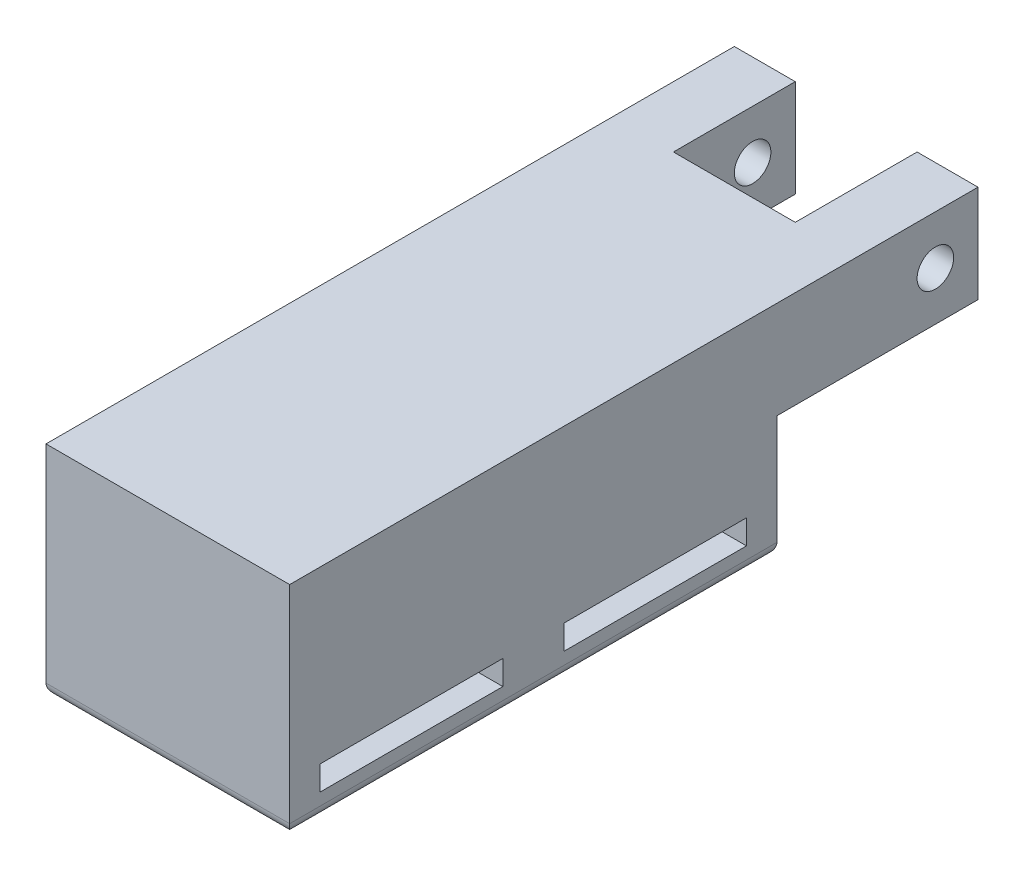
SolidWorks part; units mm, degrees
ref_plane "Alzado" through (0, 0, 0) normal (0, 0, 1) x (1, 0, 0)
ref_plane "Planta" through (0, 0, 0) normal (0, 1, 0) x (1, 0, 0)
ref_plane "Vista lateral" through (0, 0, 0) normal (1, 0, 0) x (0, 0, -1)
sketch "Croquis1" plane through (0, 0, 0) normal (1, 0, 0) x (0, 0, -1)
  line L0 (0, 9) -> (0, 1) construction
  line L9 (-1.5, 9) -> (-58, 9)
  line L18 (0, 9) -> (0, -9) construction
  line L19 (0, -9) -> (-58, -9) construction
  line L25 (0, 1) -> (-18, 1) construction
  line L26 (0, 1) -> (0, -2.6179) construction
  line L29 (0, -2.6179) -> (0, -9) construction
  line L31 (-1.5, 9) -> (-1.5, 1)
  line L32 (-18, 1) -> (-1.5, 1)
  line L35 (-58, -9) -> (-18, -9)
  line L56 (-58, 9) -> (-58, -9)
  line L59 (0, 9) -> (-58, 9) construction
  line L61 (-18, 1) -> (-18, -9)
  circle A0 centre (-5, 5) radius 1.5
  point P5 (0, 0)
  point P7 (0, 0)
  point P9 (0, 0)
  point P11 (-32.3135, 7.75)
  point P12 (0, 5)
  point P13 (-0.5889, 7.75)
  dimension "D6" = 3
  dimension "D1" = 58
  dimension "D2" = 10
  dimension "D3" = 40
  dimension "D4" = 8
  dimension "D7" = 5
  dimension "D8" = 3
extrude "Saliente-Extruir1" add sketch "Croquis1" along normal mid plane 20
sketch "Croquis2" plane through (0, 0, 0) normal (0, 1, 0) x (1, 0, 0)
  line L5 (10, -1.5) -> (-10, -1.5) construction
  line L8 (-5, -1.5) -> (5, -1.5)
  line L9 (-5, -1.5) -> (-5, -11.5)
  line L10 (-5, -11.5) -> (5, -11.5)
  line L11 (5, -1.5) -> (5, -11.5)
  point P4 (0, 0)
  point P5 (-5, -9.7017)
  point P6 (0, -1.5)
  dimension "D1" = 10
  dimension "D2" = 10
extrude "Cortar-Extruir1" cut sketch "Croquis2" against normal through all both and the other way through all
sketch "Croquis4" plane through (0, 0, 0) normal (1, 0, 0) x (0, 0, -1)
  line L0 (-58, -9) -> (-18, -9) construction
  line L1 (-55.5, -5) -> (-40.5, -5)
  line L2 (-55.5, -5) -> (-55.5, -7)
  line L3 (-55.5, -7) -> (-40.5, -7)
  line L4 (-40.5, -5) -> (-40.5, -7)
  line L5 (-55.5, -5) -> (-40.5, -7) construction
  line L6 (-55.5, -7) -> (-40.5, -5) construction
  line L7 (-18, -9) -> (-18, 1) construction
  line L8 (-35.5, -5) -> (-20.5, -5)
  line L9 (-35.5, -5) -> (-35.5, -7)
  line L10 (-35.5, -7) -> (-20.5, -7)
  line L11 (-20.5, -5) -> (-20.5, -7)
  line L12 (-58, 9) -> (-58, -9) construction
  point P0 (-48, -6)
  point P7 (-28, -7)
  point P16 (-48, -7)
  dimension "D1" = 2
  dimension "D2" = 2
  dimension "D3" = 15
  dimension "D4" = 10
  dimension "D5" = 10
extrude "Cortar-Extruir4" cut sketch "Croquis4" against normal through all both and the other way through all
fillet "Redondeo2" radius 1 4 edges at (10, -9, 38) (-10, -9, 38) (0, -9, 58) (0, -9, 18)
